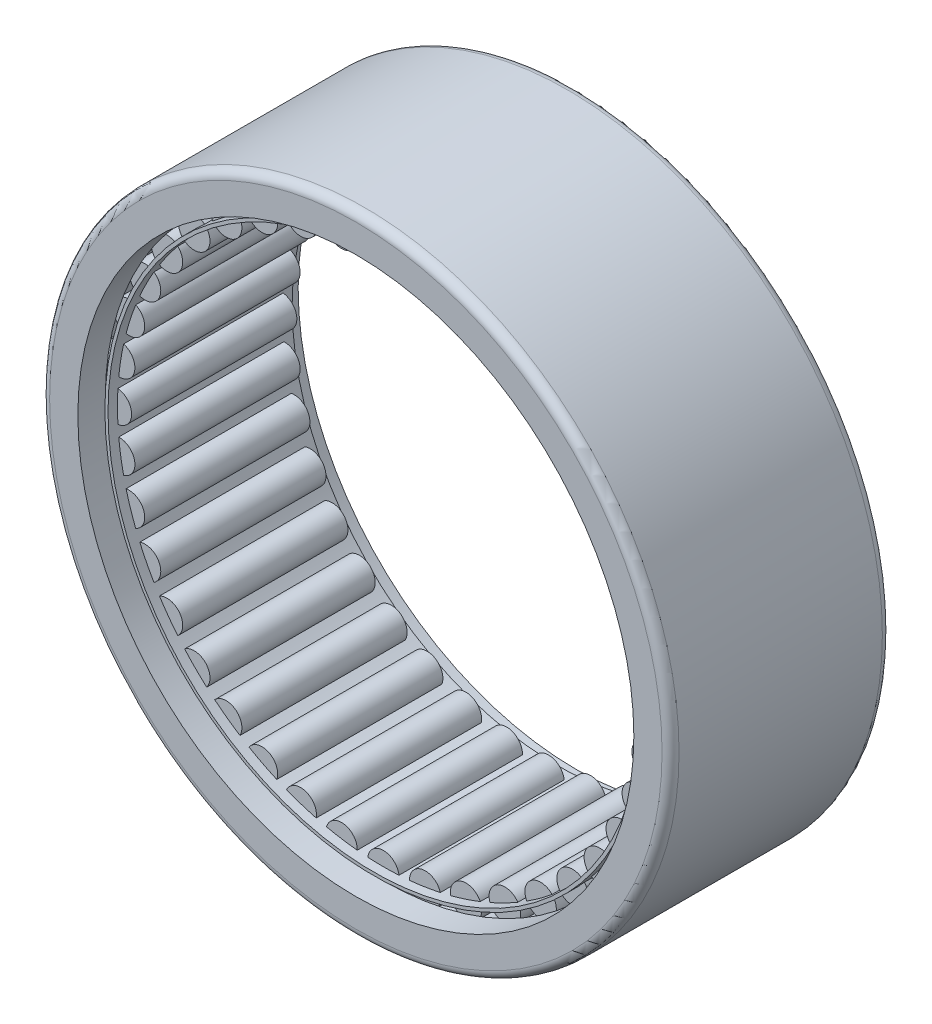
SolidWorks part; units mm, degrees
ref_plane "Front Plane" through (0, 0, 0) normal (0, 0, 1) x (1, 0, 0)
ref_plane "Top Plane" through (0, 0, 0) normal (0, 1, 0) x (1, 0, 0)
ref_plane "Right Plane" through (0, 0, 0) normal (1, 0, 0) x (0, 0, -1)
sketch "BaseSke" plane through (0, 0, 0) normal (1, 0, 0) x (0, 0, -1)
  line L0 (-47.2296, 0) -> (24.6132, 0) construction
  line L1 (-47.2296, 42.5) -> (24.6132, 42.5) construction
  line L2 (0, 129.5214) -> (0, -86.3012) construction
  line L3 (-13.125, 42.5) -> (-13.125, 45) construction
  line L4 (-17.5, 50) -> (17.5, 50) construction
  line L5 (-17.5, 35) -> (17.5, 35) construction
  line L6 (-13.125, 40) -> (13.125, 40)
  line L7 (-13.125, 40) -> (-13.125, 42.5)
  line L8 (-13.125, 42.5) -> (13.125, 42.5)
  line L9 (13.125, 40) -> (13.125, 42.5)
  line L10 (-13.125, 45) -> (13.125, 45) construction
  line L11 (13.125, 45) -> (13.125, 42.5) construction
  dimension "D2" = 26.25
  dimension "D1" = 85
revolve "Roller" add sketch "BaseSke" angle 360 about L8
sketch "OuterRaceSke" plane through (0, 0, 0) normal (1, 0, 0) x (0, 0, -1)
  line L0 (0, 0) -> (0, 87.5396) construction
  line L1 (-17.5, 50) -> (17.5, 50)
  line L2 (-17.5, 50) -> (-17.5, 44.1667)
  line L3 (-17.5, 44.1667) -> (-13.15, 44.1667)
  line L4 (17.5, 50) -> (17.5, 44.1667)
  line L5 (-50.3916, 0) -> (55.2197, 0) construction
  line L6 (-13.125, 45) -> (13.125, 45) construction
  line L7 (13.15, 44.1667) -> (17.5, 44.1667)
  line L9 (-13.15, 44.1667) -> (-13.15, 44.98)
  line L10 (-13.15, 44.98) -> (13.15, 44.98)
  line L11 (13.15, 44.1667) -> (13.15, 44.98)
  dimension "D2" = 88.3333
  dimension "D1" = 26.3
  dimension "D3" = 0.02
revolve "OuterRace" add sketch "OuterRaceSke" angle 360 about L5
sketch "CageSke" plane through (0, 0, 0) normal (1, 0, 0) x (0, 0, -1)
  line L0 (-70.8626, 0) -> (113.5527, 0) construction
  line L1 (0, 58.441) -> (0, -70.8113) construction
  line L2 (-14.625, 42.25) -> (14.625, 42.25)
  line L3 (-14.625, 42.25) -> (-14.625, 42.75)
  line L4 (-33.2996, 42.5) -> (13.017, 42.5) construction
  line L5 (-47.2296, 42.5) -> (24.6132, 42.5) construction
  line L6 (0, 129.5214) -> (0, -86.3012) construction
  line L7 (-14.625, 42.75) -> (14.625, 42.75)
  line L9 (14.625, 42.25) -> (14.625, 42.75)
  point P17 (0, 42.25)
  dimension "D1" = 29.25
  dimension "D2" = 0.5
revolve "Cage" add sketch "CageSke" angle 360 about L0
fillet "Fillet1" radius 1.35 2 edges at (50, 0, -17.5) (50, 0, 17.5)
pattern_circular "CirPatternBall" count 40 over 360 about axis through (0, 0, 50.3916) along (0, 0, -1) of "Roller"
sketch "SimplifiedSke" plane through (0, 0, 0) normal (1, 0, 0) x (0, 0, -1)
  line L0 (37.5911, 0) -> (-37.5911, 0) construction
  line L1 (-13.1351, 42.5) -> (13.151, 42.5) construction
  line L2 (-13.125, 45) -> (13.125, 45)
  line L3 (-13.125, 45) -> (-13.125, 40)
  line L4 (-13.125, 40) -> (13.125, 40)
  line L5 (13.125, 45) -> (13.125, 40)
  line L6 (-47.2296, 42.5) -> (24.6132, 42.5) construction
revolve "Simplified" [suppressed] add sketch "SimplifiedSke" angle 360 about L0
equation "\"D2@BaseSke\" = \"Bearing_Thickness@BaseSke\"*0.75"
equation "\"D1@BaseSke\" =  ( \"Bearing_Outside_Diameter@BaseSke\" + \"Bearing_Inside_Diameter@BaseSke\" )  / 2"
equation "\"D1@OuterRaceSke\" = \"Bearing_Thickness@BaseSke\"*0.75+0.05"
equation "\"D2@OuterRaceSke\" =\"D1@BaseSke\" +  ( \"D1@BaseSke\" - \"Diameter_Fw@BaseSke\" )  / 1.5"
equation "\"D1@CageSke\" = \"Bearing_Thickness@BaseSke\"*0.75+3"
equation "\"D2@CageSke\" = ( \"Bearing_Outside_Diameter@BaseSke\" - \"Diameter_Fw@BaseSke\" ) *0.025"
equation "\"D1@CirPatternBall\" =  int(  ( \"Bearing_Outside_Diameter@BaseSke\" + \"Bearing_Inside_Diameter@BaseSke\" )  / 2 *  pi  /  ( \"Bearing_Outside_Diameter@BaseSke\" - \"Bearing_Inside_Diameter@BaseSke\" ) * 4.5 ) "
